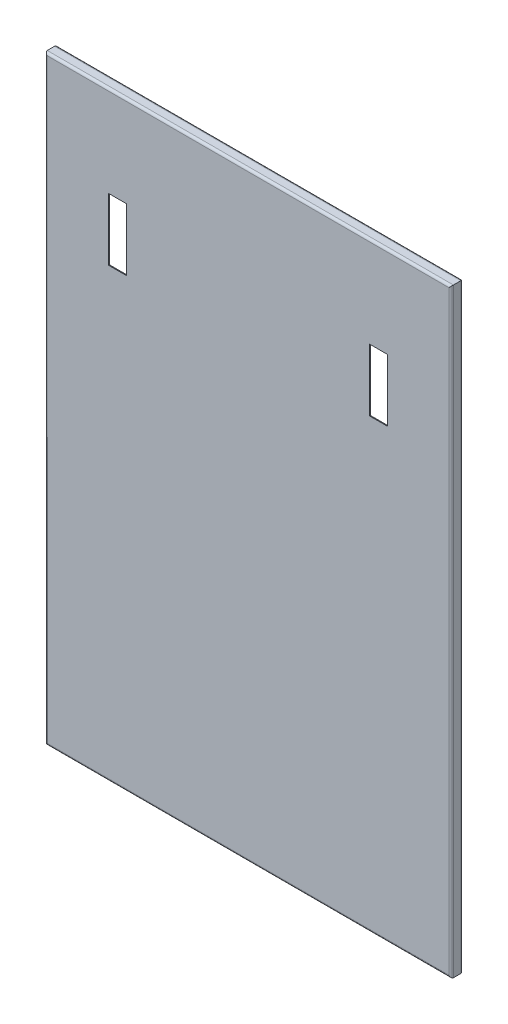
SolidWorks part; units mm, degrees
ref_plane "정면" through (0, 0, 0) normal (0, 0, 1) x (1, 0, 0)
ref_plane "윗면" through (0, 0, 0) normal (0, 1, 0) x (1, 0, 0)
ref_plane "우측면" through (0, 0, 0) normal (1, 0, 0) x (0, 0, -1)
sketch "스케치1" plane through (0, 0, 0) normal (0, 0, 1) x (1, 0, 0)
  line L1 (0, 0) -> (568, 0)
  line L2 (0, 0) -> (0, 839)
  line L3 (0, 839) -> (568, 839)
  line L4 (568, 0) -> (568, 839)
  dimension "D1" = 839
  dimension "D2" = 568
extrude "보스-돌출1" add sketch "스케치1" along normal blind 1.2
sketch "스케치2" plane through (0, 0, 1.2) normal (0, 0, 1) x (1, 0, 0)
  line L0 (0, 0) -> (568, 0) construction
  line L1 (89, 712) -> (114, 712)
  line L2 (89, 712) -> (89, 625)
  line L3 (89, 625) -> (114, 625)
  line L4 (114, 712) -> (114, 625)
  line L5 (454, 712) -> (479, 712)
  line L6 (454, 712) -> (454, 625)
  line L7 (454, 625) -> (479, 625)
  line L8 (479, 712) -> (479, 625)
  line L9 (0, 839) -> (0, 0) construction
  dimension "D1" = 625
  dimension "D2" = 87
  dimension "D3" = 89
  dimension "D4" = 25
  dimension "D5" = 340
  dimension "D6" = 25
extrude "컷-돌출1" cut sketch "스케치2" against normal through all
sketch "스케치3" plane through (0, 0, 0) normal (0, 0, -1) x (-1, 0, 0)
  line L0 (-1.2, 837.8) -> (-566.8, 837.8)
  line L1 (-566.8, 837.8) -> (-566.8, 1.2)
  line L2 (-566.8, 1.2) -> (-1.2, 1.2)
  line L3 (-1.2, 1.2) -> (-1.2, 837.8)
  line L4 (0, 0) -> (0, 839)
  line L5 (0, 839) -> (-568, 839)
  line L6 (-568, 839) -> (-568, 0)
  line L7 (-568, 0) -> (0, 0)
  line L8 (0, 0) -> (0, 839)
  line L9 (0, 839) -> (-568, 839)
  line L10 (-568, 839) -> (-568, 0)
  line L11 (-568, 0) -> (0, 0)
  dimension "D1" = 0
  dimension "D2" = 1.2
extrude "보스-돌출2" add sketch "스케치3" along normal blind 15.5
sketch "스케치4" plane through (0, 0, -15.5) normal (0, 0, -1) x (-1, 0, 0)
  line L0 (-15, 824) -> (-553, 824)
  line L1 (-553, 824) -> (-553, 15)
  line L2 (-553, 15) -> (-15, 15)
  line L3 (-15, 15) -> (-15, 824)
  line L4 (-568, 0) -> (0, 0)
  line L5 (0, 0) -> (0, 839)
  line L6 (0, 839) -> (-568, 839)
  line L7 (-568, 839) -> (-568, 0)
  line L8 (-568, 0) -> (0, 0)
  line L9 (0, 0) -> (0, 839)
  line L10 (0, 839) -> (-568, 839)
  line L11 (-568, 839) -> (-568, 0)
  dimension "D1" = 0
  dimension "D2" = 15
extrude "보스-돌출3" add sketch "스케치4" against normal blind 1.2
fillet "필렛1" radius 3.2 4 edges at (284, 0, 1.2) (568, 419.5, 1.2) (284, 839, 1.2) (0, 419.5, 1.2)
fillet "필렛3" radius 2 4 edges at (284, 1.2, 0) (566.8, 419.5, 0) (284, 837.8, 0) (1.2, 419.5, 0)
fillet "필렛4" radius 3.2 4 edges at (284, 0, -15.5) (0, 419.5, -15.5) (568, 419.5, -15.5) (284, 839, -15.5)
fillet "필렛5" radius 2 2 edges at (284, 837.8, -14.3) (284, 1.2, -14.3)
fillet "필렛6" radius 2 14 edges at (566.2142, 837.2142, -0.5858) (566.8, 837.8, -7.15) (566.8, 837.2142, -13.7142) (566.8, 419.5, -14.3) (566.8, 1.7858, -13.7142) (566.2142, 1.7858, -0.5858) (1.7858, 1.7858, -0.5858) (1.2, 1.2, -7.15) (1.2, 1.7858, -13.7142) (1.7858, 837.2142, -0.5858) (1.2, 837.8, -7.15) (1.2, 837.2142, -13.7142) (566.8, 1.2, -7.15) (1.2, 419.5, -14.3)
